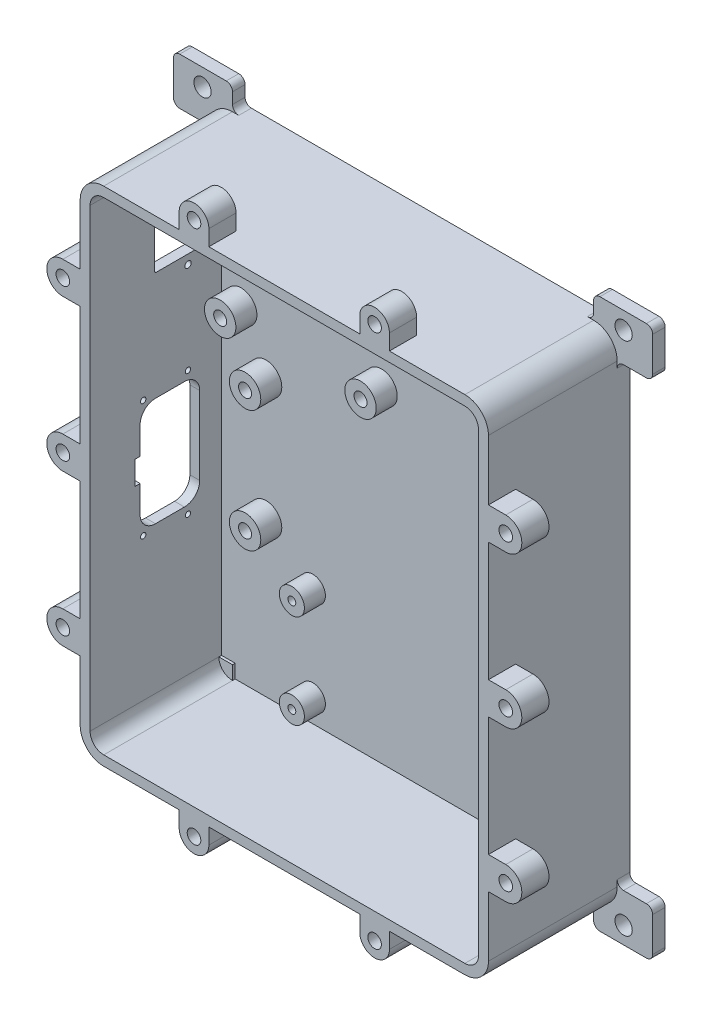
SolidWorks part; units mm, degrees
material "ABS"
ref_plane "X-Y Datum" through (0, 0, 0) normal (0, 0, 1) x (1, 0, 0)
ref_plane "X-Z Datum" through (0, 0, 0) normal (0, 1, 0) x (1, 0, 0)
ref_plane "Y-Z Datum" through (0, 0, 0) normal (1, 0, 0) x (0, 0, -1)
sketch "Sketch1" plane through (0, 0, 0) normal (0, 0, 1) x (1, 0, 0)
  line L1 (-82.55, 101.6) -> (82.55, 101.6)
  line L2 (-82.55, 101.6) -> (-82.55, -101.6)
  line L3 (-82.55, -101.6) -> (82.55, -101.6)
  line L4 (82.55, 101.6) -> (82.55, -101.6)
  line L5 (-82.55, 101.6) -> (82.55, -101.6) construction
  line L6 (-82.55, -101.6) -> (82.55, 101.6) construction
  point P0 (0, 0)
  dimension "D1" = 165.1
  dimension "D2" = 203.2
extrude "Boss-Extrude1" add sketch "Sketch1" along normal blind 57.15
fillet "Fillet1" radius 9.525 4 edges at (82.55, 101.6, 28.575) (-82.55, 101.6, 28.575) (-82.55, -101.6, 28.575) (82.55, -101.6, 28.575)
shell "Shell1" thickness 4 removed face at (0, 0, 57.15)
sketch "Sketch2" plane through (0, 0, 4) normal (0, 0, 1) x (1, 0, 0)
  line L0 (0, -97.6) -> (0, 97.6) construction
  line L1 (-73.025, -97.6) -> (73.025, -97.6) construction
  line L2 (73.025, 97.6) -> (-73.025, 97.6) construction
  line L3 (-78.55, 92.075) -> (-78.55, -92.075) construction
  line L4 (-44.45, -47.308) -> (44.45, -47.308) construction
  line L5 (-44.45, -47.308) -> (-44.45, -91.25) construction
  line L6 (-44.45, -91.25) -> (44.45, -91.25) construction
  line L7 (44.45, -47.308) -> (44.45, -91.25) construction
  line L8 (-44.45, -47.308) -> (44.45, -91.25) construction
  line L9 (-44.45, -91.25) -> (44.45, -47.308) construction
  line L10 (-41.6, -50.279) -> (41.6, -50.279) construction
  line L11 (-41.6, -50.279) -> (-41.6, -88.279) construction
  line L12 (-41.6, -88.279) -> (41.6, -88.279) construction
  line L13 (41.6, -50.279) -> (41.6, -88.279) construction
  line L14 (-41.6, -50.279) -> (41.6, -88.279) construction
  line L15 (-41.6, -88.279) -> (41.6, -50.279) construction
  line L16 (-78.55, 92.075) -> (-78.55, -92.075)
  line L17 (73.025, 97.6) -> (-73.025, 97.6) construction
  line L18 (-60.516, 14.011) -> (61.1507, 14.011) construction
  line L19 (-60.516, 14.011) -> (-60.516, -35.221) construction
  line L20 (-60.516, -35.221) -> (61.1507, -35.221) construction
  line L21 (61.1507, 14.011) -> (61.1507, -35.221) construction
  line L22 (-60.516, 14.011) -> (61.1507, -35.221) construction
  line L23 (-60.516, -35.221) -> (61.1507, 14.011) construction
  line L24 (-70.58, 84.245) -> (59.42, 84.245) construction
  line L25 (-70.58, 84.245) -> (-70.58, 34.245) construction
  line L26 (-70.58, 34.245) -> (59.42, 34.245) construction
  line L27 (59.42, 84.245) -> (59.42, 34.245) construction
  line L28 (-70.58, 84.245) -> (59.42, 34.245) construction
  line L29 (-70.58, 34.245) -> (59.42, 84.245) construction
  line L30 (-72.0727, 19.748) -> (72.7073, 19.748) construction
  line L31 (-72.0727, 19.748) -> (-72.0727, -40.958) construction
  line L32 (-72.0727, -40.958) -> (72.7073, -40.958) construction
  line L33 (72.7073, 19.748) -> (72.7073, -40.958) construction
  line L34 (-72.0727, 19.748) -> (72.7073, -40.958) construction
  line L35 (-72.0727, -40.958) -> (72.7073, 19.748) construction
  line L36 (-72.255, 89.217) -> (61.095, 89.217) construction
  line L37 (-72.255, 89.217) -> (-72.255, 29.273) construction
  line L38 (-72.255, 29.273) -> (61.095, 29.273) construction
  line L39 (61.095, 89.217) -> (61.095, 29.273) construction
  line L40 (-72.255, 89.217) -> (61.095, 29.273) construction
  line L41 (-72.255, 29.273) -> (61.095, 89.217) construction
  line L42 (-44.8662, 59.245) -> (33.7062, 59.245) construction
  circle A1 centre (-41.6, -88.279) radius 5.08
  circle A2 centre (41.6, -88.279) radius 5.08
  circle A3 centre (41.6, -50.279) radius 5.08
  circle A4 centre (-41.6, -50.279) radius 5.08
  circle A5 centre (-60.516, -35.221) radius 6.35
  circle A6 centre (61.1507, -35.221) radius 6.35
  circle A7 centre (61.1507, 14.011) radius 6.35
  circle A8 centre (-60.516, 14.011) radius 6.35
  circle A9 centre (-70.58, 34.245) radius 6.35
  circle A10 centre (59.42, 34.245) radius 6.35
  circle A11 centre (-70.58, 84.245) radius 6.35
  circle A12 centre (59.42, 84.245) radius 6.35
  circle A13 centre (-13.83, 34.245) radius 6.35
  circle A14 centre (-13.83, 84.245) radius 6.35
  point P6 (0, -69.279)
  point P11 (0, -69.279)
  point P18 (0.3173, -10.605)
  point P23 (-5.58, 59.245)
  point P28 (-5.58, 59.245)
  point P29 (0.3173, -10.605)
  point P57 (-5.58, 59.245)
  dimension "D22" = 12.7
  dimension "D1" = 43.942
  dimension "D2" = 88.9
  dimension "D3" = 83.2
  dimension "D4" = 38
  dimension "D5" = 18.034
  dimension "D6" = 121.6667
  dimension "D7" = 49.232
  dimension "D8" = 7.97
  dimension "D9" = 130
  dimension "D10" = 50
  dimension "D11" = 6.35
  dimension "D12" = 144.78
  dimension "D13" = 60.706
  dimension "D14" = 59.944
  dimension "D15" = 133.35
  dimension "D16" = 6.35
  dimension "D17" = 9.525
  dimension "D18" = 8.383
  dimension "D20" = 56.75
extrude "Boss-Extrude2" add sketch "Sketch2" along normal blind 8.5 contours A4 | A1 | A2 | A3 region at (-41.6, -88.279, 4) region at (41.6, -88.279, 4) region at (41.6, -50.279, 4) region at (-41.6, -50.279, 4)
sketch "Sketch3" plane through (0, 0, 12.5) normal (0, 0, 1) x (1, 0, 0)
  circle A0 centre (-41.6, -88.279) radius 1.5875
  circle A1 centre (41.6, -88.279) radius 1.5875
  circle A2 centre (41.6, -50.279) radius 1.5875
  circle A4 centre (-41.6, -50.279) radius 1.5875
extrude "Cut-Extrude1" cut sketch "Sketch3" against normal blind 5 contours A4 | A0 | A1 | A2 region at (-41.6, -88.279, 12.5) region at (41.6, -88.279, 12.5) region at (41.6, -50.279, 12.5) region at (-41.6, -50.279, 12.5)
extrude "Boss-Extrude6" add sketch "Sketch2<3>" along normal blind 8.5 contours A5 | A8 | A6 | A7 | A13 | A9 | A11 | A14 | A12 | A10 region at (-60.516, -35.221, 4) region at (61.1507, -35.221, 4) region at (61.1507, 14.011, 4) region at (-60.516, 14.011, 4) region at (-70.58, 34.245, 4) region at (59.42, 34.245, 4) region at (-70.58, 84.245, 4) region at (59.42, 84.245, 4) region at (-13.83, 34.245, 4) region at (-13.83, 84.245, 4)
sketch "Sketch2<3>" plane through (0, 0, 4) normal (0, 0, 1) x (1, 0, 0) same geometry as "Sketch2"
sketch "Sketch13" plane through (0, 0, 12.5) normal (0, 0, 1) x (1, 0, 0)
  circle A0 centre (-60.516, -35.221) radius 2.625
  circle A1 centre (61.1507, -35.221) radius 2.625
  circle A2 centre (61.1507, 14.011) radius 2.625
  circle A3 centre (-60.516, 14.011) radius 2.625
  circle A4 centre (-13.83, 34.245) radius 2.625
  circle A5 centre (-70.58, 34.245) radius 2.625
  circle A6 centre (59.42, 34.245) radius 2.625
  circle A7 centre (59.42, 84.245) radius 2.625
  circle A8 centre (-13.83, 84.245) radius 2.625
  circle A9 centre (-70.58, 84.245) radius 2.625
extrude "Cut-Extrude5" cut sketch "Sketch13" against normal blind 7
sketch "Sketch4" plane through (0, 0, 57.15) normal (0, 0, 1) x (1, 0, 0)
  line L0 (-82.55, 92.075) -> (-82.55, -92.075) construction
  line L1 (-73.025, -101.6) -> (73.025, -101.6) construction
  line L2 (-82.55, 92.075) -> (-82.55, -92.075)
  line L3 (-73.025, -101.6) -> (73.025, -101.6)
  line L4 (-82.55, 0) -> (-89.55, 0) construction
  line L5 (-89.55, 6.5) -> (-82.55, 6.5)
  line L6 (-89.55, -6.5) -> (-82.55, -6.5)
  line L7 (-73.025, -101.6) -> (0, -101.6)
  line L8 (-36.5125, -101.6) -> (-36.5125, -108.6) construction
  line L9 (0, -101.6) -> (0, -117.385) construction
  line L10 (-30.0125, -108.6) -> (-30.0125, -101.6)
  line L11 (-43.0125, -108.6) -> (-43.0125, -101.6)
  line L12 (30.0125, -108.6) -> (30.0125, -101.6)
  line L13 (36.5125, -101.6) -> (36.5125, -108.6) construction
  line L14 (43.0125, -108.6) -> (43.0125, -101.6)
  circle A0 centre (-89.55, 0) radius 2.75
  circle A1 centre (-89.55, 0) radius 6.5
  circle A2 centre (-36.5125, -108.6) radius 6.5
  circle A3 centre (-36.5125, -108.6) radius 2.75
  circle A4 centre (36.5125, -108.6) radius 2.75
  circle A5 centre (36.5125, -108.6) radius 6.5
  point P13 (0, -101.6)
  dimension "D1" = 5.5
  dimension "D2" = 13
  dimension "D3" = 7
  dimension "D4" = 146.05
  dimension "D5" = 73.025
extrude "Boss-Extrude3" add sketch "Sketch4" against normal blind 11 contours A1 L6 L2 L5 | A1 | A0 region at (-82.6976, 0, 57.15) region at (-85.0838, 4.4662, 57.15) region at (-89.55, 0, 57.15)
extrude "Cut-Extrude2" cut sketch "Sketch4<6>" against normal blind 8 and the other way through all contours A0 region at (-89.55, 0, 57.15)
sketch "Sketch4<6>" plane through (0, 0, 57.15) normal (0, 0, 1) x (1, 0, 0) same geometry as "Sketch4"
pattern_linear "LPattern1" count 2 spacing 61.214 along (0, 1, 0) count 2 spacing 61.214 along (0, -1, 0) of "Boss-Extrude3", "Cut-Extrude2"
mirror "Mirror1" about plane through (0, 0, 0) normal (1, 0, 0) of "LPattern1"
sketch "Sketch12" plane through (0, 0, 57.15) normal (0, 0, 1) x (1, 0, 0)
  line L0 (-73.025, -101.6) -> (73.025, -101.6) construction
  line L1 (-73.025, -101.6) -> (73.025, -101.6)
  line L2 (0, -101.6) -> (0, -113.5544) construction
  line L3 (-73.025, -101.6) -> (0, -101.6)
  line L4 (0, -101.6) -> (-36.5125, -101.6)
  line L5 (-36.5125, -101.6) -> (-36.5125, -107.95) construction
  line L6 (-42.5125, -107.95) -> (-42.5125, -101.6)
  line L7 (-30.5125, -107.95) -> (-30.5125, -101.6)
  line L8 (30.5125, -107.95) -> (30.5125, -101.6)
  line L9 (36.5125, -101.6) -> (36.5125, -107.95) construction
  line L10 (42.5125, -107.95) -> (42.5125, -101.6)
  circle A0 centre (-36.5125, -107.95) radius 6
  circle A1 centre (-36.5125, -107.95) radius 2.75
  circle A2 centre (36.5125, -107.95) radius 6
  circle A3 centre (36.5125, -107.95) radius 2.75
  line M16 (-73.025, -101.6) -> (73.025, -101.6)
  dimension "D1" = 12
  dimension "D2" = 5.5
  dimension "D3" = 6.35
extrude "Boss-Extrude5" add sketch "Sketch12" against normal blind 11 contours A0 A1 | A0 L7 L3 L6 | L8 A2 L10 M16 | A2 A3 | A3 | A1 region at (36.5125, -101.7358, 57.15) region at (-39.5125, -101.7358, 57.15) region at (-36.5125, -102.1197, 57.15) region at (36.5125, -102.1197, 57.15) region at (-36.5125, -107.95, 57.15) region at (36.5125, -107.95, 57.15)
extrude "Cut-Extrude3" cut sketch "Sketch12<3>" against normal blind 8 contours A1 | A3 region at (-36.5125, -107.95, 57.15) region at (36.5125, -107.95, 57.15)
sketch "Sketch12<3>" plane through (0, 0, 57.15) normal (0, 0, 1) x (1, 0, 0) same geometry as "Sketch12"
mirror "Mirror2" about plane through (0, 0, 0) normal (0, 1, 0) of "Cut-Extrude3", "Boss-Extrude5"
sketch "Sketch14" plane through (-82.55, 0, 0) normal (-1, 0, 0) x (0, 0, 1)
  line L0 (13.0012, 71.1737) -> (13.0012, 55.9242)
  line L1 (57.15, 92.075) -> (0, 92.075) construction
  line L2 (57.15, 92.075) -> (57.15, -92.075) construction
  line L3 (57.15, -92.075) -> (0, -92.075) construction
  line L4 (0, 92.075) -> (0, -92.075) construction
  line L5 (13.8012, 71.0239) -> (30.2512, 71.0239) construction
  line L6 (13.8012, 71.0239) -> (13.8012, 56.0739) construction
  line L7 (13.8012, 56.0739) -> (30.2512, 56.0739) construction
  line L8 (30.2512, 71.0239) -> (30.2512, 56.0739) construction
  line L9 (13.8012, 71.0239) -> (30.2512, 56.0739) construction
  line L10 (13.8012, 56.0739) -> (30.2512, 71.0239) construction
  line L11 (13.6514, 55.2739) -> (30.401, 55.2739)
  line L12 (31.0512, 71.1737) -> (31.0512, 55.9242)
  line L13 (13.6514, 71.8239) -> (30.401, 71.8239)
  line L14 (13.0564, 11.0195) -> (36.6564, 11.0195) construction
  line L15 (13.0564, 11.0195) -> (13.0564, -32.3771) construction
  line L16 (13.0564, -32.3771) -> (36.6564, -32.3771) construction
  line L17 (36.6564, 11.0195) -> (36.6564, -6.1788) construction
  line L18 (13.0564, 11.0195) -> (36.6564, -32.3771) construction
  line L19 (13.0564, -32.3771) -> (36.6564, 11.0195) construction
  line L20 (36.6564, -6.1788) -> (38.6564, -6.1788) construction
  line L21 (38.6564, -6.1788) -> (38.6564, -15.1788) construction
  line L22 (38.6564, -15.1788) -> (36.6564, -15.1788) construction
  line L23 (36.6564, -15.1788) -> (36.6564, -32.3771) construction
  line L24 (19.0026, 11.2735) -> (30.7103, 11.2735)
  line L25 (36.9104, 5.0734) -> (36.9104, -5.9248)
  line L26 (36.9104, -5.9248) -> (38.9104, -5.9248)
  line L27 (38.9104, -5.9248) -> (38.9104, -15.4328)
  line L28 (38.9104, -15.4328) -> (36.9104, -15.4328)
  line L29 (36.9104, -15.4328) -> (36.9104, -26.431)
  line L30 (19.0026, -32.6311) -> (30.7103, -32.6311)
  line L31 (12.8024, 5.0734) -> (12.8024, -26.431)
  arc A0 (36.9104, -26.431) -> (30.7103, -32.6311) centre (30.7103, -26.431) cw
  arc A1 (19.0026, -32.6311) -> (12.8024, -26.431) centre (19.0026, -26.431) cw
  arc A2 (19.0026, 11.2735) -> (12.8024, 5.0734) centre (19.0026, 5.0734) ccw
  arc A3 (30.7103, 11.2735) -> (36.9104, 5.0734) centre (30.7103, 5.0734) cw
  arc A4 (30.401, 55.2739) -> (31.0512, 55.9242) centre (30.401, 55.9242) ccw
  arc A5 (13.0012, 55.9242) -> (13.6514, 55.2739) centre (13.6514, 55.9242) ccw
  arc A6 (13.0012, 71.1737) -> (13.6514, 71.8239) centre (13.6514, 71.1737) cw
  arc A7 (31.0512, 71.1737) -> (30.401, 71.8239) centre (30.401, 71.1737) ccw
  point P4 (22.0262, 63.5489)
  point P13 (24.8564, -10.6788)
  dimension "D1" = 6.2001
  dimension "D2" = 0.6502
extrude "Cut-Extrude6" cut sketch "Sketch14" against normal up to surface (4 mm away) up to face at (-78.55, 0, 30.575)
sketch "Sketch15" plane through (-82.55, 0, 0) normal (-1, 0, 0) x (0, 0, 1)
  line L0 (13.0012, 71.8239) -> (13.0012, 55.2739) construction
  line L1 (57.15, 92.075) -> (0, 92.075) construction
  line L2 (57.15, 92.075) -> (57.15, -92.075) construction
  line L3 (57.15, -92.075) -> (0, -92.075) construction
  line L4 (0, 92.075) -> (0, -92.075) construction
  line L5 (13.8012, 71.0239) -> (30.2512, 71.0239) construction
  line L6 (13.8012, 71.0239) -> (13.8012, 56.0739) construction
  line L7 (13.8012, 56.0739) -> (30.2512, 56.0739) construction
  line L8 (30.2512, 71.0239) -> (30.2512, 56.0739) construction
  line L9 (13.8012, 71.0239) -> (30.2512, 56.0739) construction
  line L10 (13.8012, 56.0739) -> (30.2512, 71.0239) construction
  line L11 (13.0012, 55.2739) -> (31.0512, 55.2739) construction
  line L12 (31.0512, 71.8239) -> (31.0512, 55.2739) construction
  line L13 (13.0012, 71.8239) -> (31.0512, 71.8239) construction
  line L14 (13.0564, 11.0195) -> (36.6564, 11.0195) construction
  line L15 (13.0564, 11.0195) -> (13.0564, -32.3771) construction
  line L16 (13.0564, -32.3771) -> (36.6564, -32.3771) construction
  line L17 (36.6564, 11.0195) -> (36.6564, -6.1788) construction
  line L18 (13.0564, 11.0195) -> (36.6564, -32.3771) construction
  line L19 (13.0564, -32.3771) -> (36.6564, 11.0195) construction
  line L20 (36.6564, -6.1788) -> (38.6564, -6.1788) construction
  line L21 (38.6564, -6.1788) -> (38.6564, -15.1788) construction
  line L22 (38.6564, -15.1788) -> (36.6564, -15.1788) construction
  line L23 (36.6564, -15.1788) -> (36.6564, -32.3771) construction
  line L24 (12.8024, 11.2735) -> (36.9104, 11.2735) construction
  line L25 (36.9104, 11.2735) -> (36.9104, -5.9248) construction
  line L26 (36.9104, -5.9248) -> (38.9104, -5.9248) construction
  line L27 (38.9104, -5.9248) -> (38.9104, -15.4328) construction
  line L28 (38.9104, -15.4328) -> (36.9104, -15.4328) construction
  line L29 (36.9104, -15.4328) -> (36.9104, -32.6311) construction
  line L30 (12.8024, -32.6311) -> (36.9104, -32.6311) construction
  line L31 (12.8024, 11.2735) -> (12.8024, -32.6311) construction
  circle A0 centre (26.5262, 75.5489) radius 1.278
  circle A1 centre (17.5262, 51.5489) radius 1.278
  circle A2 centre (35.6564, 13.0212) radius 1.085
  circle A3 centre (17.5564, 14.5212) radius 1.085
  circle A4 centre (35.6564, -34.3788) radius 1.085
  circle A5 centre (17.5564, -35.8788) radius 1.085
  point P4 (22.0262, 63.5489)
  point P13 (24.8564, -10.6788)
  point P32 (27.8042, 75.5489)
  point P33 (17.5262, 51.5489)
  point P34 (17.5262, 50.2709)
extrude "Cut-Extrude7" cut sketch "Sketch15" against normal up to surface (4 mm away) up to face at (-78.55, -10.6788, 29.2078)
sketch "Sketch16" plane through (0, 0, 0) normal (0, 0, -1) x (-1, 0, 0)
  line L0 (-73.025, 101.6) -> (-73.025, 92.075) construction
  line L1 (-79.7602, 98.8102) -> (-85.1483, 104.1983) construction
  line L2 (-73.025, 92.075) -> (-96.8886, 92.075)
  line L3 (-73.025, 92.075) -> (-73.025, 111.125)
  line L4 (-73.025, 111.125) -> (-96.8886, 111.125)
  line L5 (-96.8886, 92.075) -> (-96.8886, 111.125)
  line L7 (-82.55, 0) -> (53.0456, 0) construction
  line L8 (-85.1483, -104.1983) -> (-84.9568, -92.075) construction
  line L9 (-85.1483, -104.1983) -> (-73.025, -101.6) construction
  line L10 (-73.025, -101.6) -> (-73.025, -92.075) construction
  line L11 (-96.8886, -92.075) -> (-96.8886, -111.125)
  line L12 (-73.025, -111.125) -> (-96.8886, -111.125)
  line L13 (-73.025, -92.075) -> (-73.025, -111.125)
  line L14 (-73.025, -92.075) -> (-96.8886, -92.075)
  line L15 (0, 101.6) -> (0, 124.0537) construction
  line L17 (73.025, -92.075) -> (96.8886, -92.075)
  line L18 (73.025, -92.075) -> (73.025, -111.125)
  line L19 (73.025, -111.125) -> (96.8886, -111.125)
  line L20 (96.8886, -92.075) -> (96.8886, -111.125)
  line L21 (85.1483, 104.1983) -> (84.9568, 92.075) construction
  line L22 (85.1483, 104.1983) -> (73.025, 101.6) construction
  line L23 (73.025, 101.6) -> (73.025, 92.075) construction
  line L24 (96.8886, 92.075) -> (96.8886, 111.125)
  line L25 (73.025, 111.125) -> (96.8886, 111.125)
  line L26 (73.025, 92.075) -> (73.025, 111.125)
  line L27 (73.025, 92.075) -> (96.8886, 92.075)
  circle A0 centre (-85.1483, 104.1983) radius 2
  circle A1 centre (-85.1483, -104.1983) radius 2
  circle A2 centre (85.1483, -104.1983) radius 2
  circle A3 centre (85.1483, 104.1983) radius 2
  arc A4 (-73.025, 101.6) -> (-82.55, 92.075) centre (-73.025, 92.075) ccw construction
extrude "Boss-Extrude7" add sketch "Sketch16" against normal blind 5.08
fillet "Fillet2" radius 2.54 20 edges at (-82.55, -92.075, 2.54) (-96.8886, -92.075, 2.54) (-73.025, -101.6, 2.54) (-73.025, -111.125, 2.54) (-96.8886, -111.125, 2.54) (73.025, -101.6, 2.54) (73.025, -111.125, 2.54) (82.55, -92.075, 2.54) (96.8886, -92.075, 2.54) (96.8886, -111.125, 2.54) (82.55, 92.075, 2.54) (96.8886, 92.075, 2.54) (73.025, 101.6, 2.54) (73.025, 111.125, 2.54) (96.8886, 111.125, 2.54) (-73.025, 101.6, 2.54) (-73.025, 111.125, 2.54) (-96.8886, 111.125, 2.54) (-82.55, 92.075, 2.54) (-96.8886, 92.075, 2.54)
hole_wizard "M6 Clearance Hole1" positions "Sketch17" profile "Sketch18" hole size "M6" standard "ANSI Metric" end condition through all
sketch "Sketch17" plane through (0, 0, 5.08) normal (0, 0, 1) x (1, 0, 0)
  point P0 (-85.1483, 104.1983)
  point P3 (85.1483, 104.1983)
  point P6 (85.1483, -104.1983)
  point P9 (-85.1483, -104.1983)
sketch "Sketch18" plane through (-85.1483, 104.1983, 5.08) normal (1, 0, 0) x (0, -1, 0)
  line L0 (0, 0) -> (0, 5.08)
  line L1 (0, 5.08) -> (3.5, 5.08)
  line L2 (3.5, 5.08) -> (3.5, 0)
  line L5 (3.5, 0) -> (0, 0)
  line L11 (0, -6.35) -> (0, 107.95) construction
  dimension "Thru Hole Dia." = 7
  dimension "Thru Hole Depth" = 5.08
